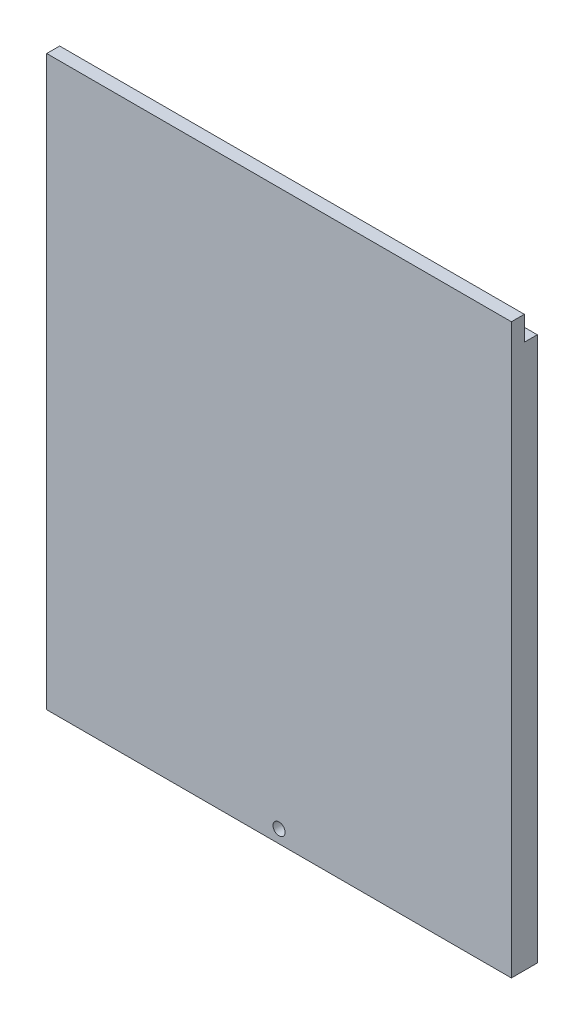
SolidWorks part; units mm, degrees
ref_plane "前视基准面" through (0, 0, 0) normal (0, 0, 1) x (1, 0, 0)
ref_plane "上视基准面" through (0, 0, 0) normal (0, 1, 0) x (1, 0, 0)
ref_plane "右视基准面" through (0, 0, 0) normal (1, 0, 0) x (0, 0, -1)
other "Configuration Table"
sketch "草图1" plane through (0, 0, 0) normal (0, 0, 1) x (1, 0, 0)
  line L61 (-26.9, 31.5) -> (26.9, 31.5)
  line L62 (-26.9, 31.5) -> (-26.9, -31.5)
  line L63 (-26.9, -31.5) -> (26.9, -31.5)
  line L64 (26.9, 31.5) -> (26.9, -31.5)
  point P4 (0, 31.5)
  point P5 (-26.9, 0)
  dimension "D1" = 63
  dimension "D2" = 53.8
extrude "凸台-拉伸1" add sketch "草图1" along normal blind 3
sketch "草图2" plane through (0, 31.5, 0) normal (0, 1, 0) x (1, 0, 0)
  line L0 (-26.9, -3) -> (-26.9, 0) construction
  line L1 (-26.9, -1.5) -> (26.9, -1.5)
  line L2 (-26.9, -1.5) -> (-26.9, -3)
  line L3 (-26.9, -3) -> (26.9, -3)
  line L4 (26.9, -1.5) -> (26.9, -3)
extrude "凸台-拉伸2" add sketch "草图2" along normal blind 2.8 contours L1 L4 L3 L2
sketch "草图3" plane through (0, 0, 0) normal (0, 0, -1) x (-1, 0, 0)
  line L0 (26.9, -31.5) -> (-26.9, -31.5) construction
  circle A4 centre (0, -30) radius 1
  circle A5 centre (0, -30) radius 0.7
  point P23 (0, 0)
  dimension "D6" = 1.4
  dimension "D7" = 2
  dimension "D5" = 1.5
extrude "切除-拉伸1" cut sketch "草图3" against normal blind 1.5 contours A4
extrude "切除-拉伸2" cut sketch "草图3<4>" against normal through all contours A5
sketch "草图3<4>" plane through (0, 0, 0) normal (0, 0, -1) x (-1, 0, 0) same geometry as "草图3"
